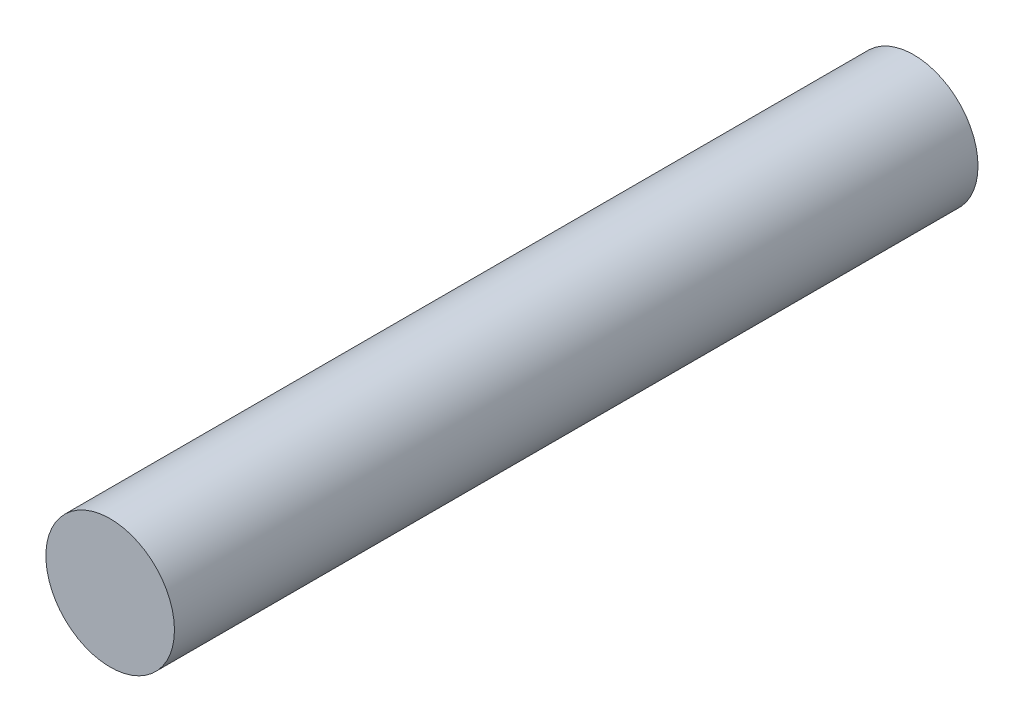
SolidWorks part; units mm, degrees
other "Папка сварных швов"
material "Ст 3 ГОСТ 380-88"
ref_plane "Front" through (0, 0, 0) normal (0, 0, 1) x (1, 0, 0)
ref_plane "Top" through (0, 0, 0) normal (0, 1, 0) x (1, 0, 0)
ref_plane "Right" through (0, 0, 0) normal (1, 0, 0) x (0, 0, -1)
sketch "Sketch1" plane through (0, 0, 0) normal (0, 0, 1) x (1, 0, 0)
  circle A0 centre (0, 0) radius 4
  point P4 (0, 0)
  dimension "D1" = 8
extrude "Boss-Extrude1" add sketch "Sketch1" along normal blind 50
ref_axis "Axis1" through (0, 0, 50) along (0, 0, -1)
ref_plane "Plane1" through (0, 0, 30) normal (0, 0, 1) x (1, 0, 0)
sketch "Sketch2" plane through (0, 0, 30) normal (0, 0, 1) x (1, 0, 0)
  point P0 (0, 0)
sketch "Sketch3" plane through (0, 0, 0) normal (1, 0, 0) x (0, 0, -1)
  line L0 (-30, 0) -> (-53.8019, 0) construction
